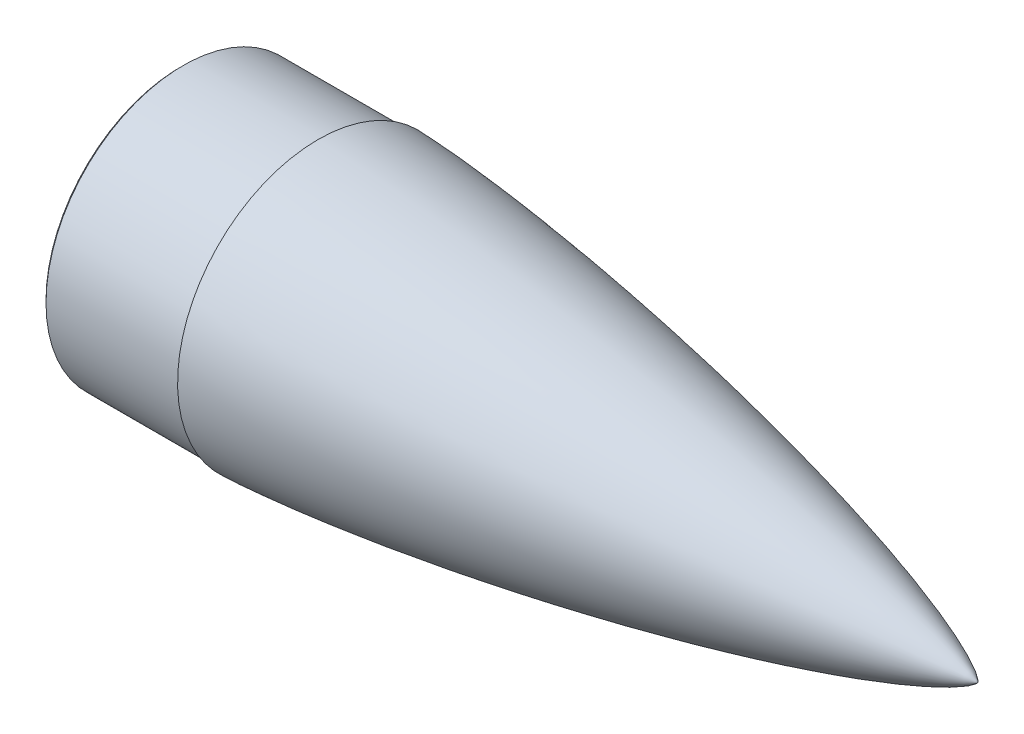
SolidWorks part; units mm, degrees
material "A-Glass Fiber"
ref_plane "Front Plane" through (0, 0, 0) normal (0, 0, 1) x (1, 0, 0)
ref_plane "Top Plane" through (0, 0, 0) normal (0, 1, 0) x (1, 0, 0)
ref_plane "Right Plane" through (0, 0, 0) normal (1, 0, 0) x (0, 0, -1)
ref_axis "Axis1" through (46.9179, 0, 0) along (-1, 0, 0)
sketch "Sketch10" plane through (0, 0, 0) normal (0, 0, 1) x (1, 0, 0)
  line L1 (-1.0327, 0) -> (486.9547, 0) construction
  line L3 (11.1125, 81.9998) -> (-84.6045, 81.9998)
  line L4 (408.9673, 0) -> (368.9673, 0)
  line L5 (-84.6045, 81.9998) -> (-84.6045, 84.9998)
  line L6 (-84.6045, 84.9998) -> (0.3953, 84.9998)
  line L7 (0.3953, 84.9998) -> (0.3953, 86.9998)
  spline S0 degree 4 poles (408.9673, 0) (408.9649, 0.0135) (408.958, 0.0399) (408.9365, 0.0905) (408.8922, 0.1741) (408.8263, 0.2756) (408.7217, 0.4158) (408.5611, 0.6051) (408.3056, 0.8724) (407.8697, 1.2753) (407.121, 1.8851) (405.8038, 2.8259) (403.4624, 4.2872) (399.3253, 6.5318) (392.4811, 9.7589) (380.6621, 14.628) (363.6372, 20.7117) (342.2152, 27.4765) (317.4285, 34.4976) (291.8793, 41.1048) (266.2105, 47.229) (240.4455, 52.9334) (214.5989, 58.2554) (188.6809, 63.2176) (165.9462, 67.2533) (146.422, 70.4938) (130.1279, 73.0449) (117.0786, 74.9942) (104.0155, 76.8485) (92.5733, 78.3845) (82.7571, 79.6356) (74.5713, 80.6322) (68.0193, 81.4008) (61.4637, 82.1394) (54.9047, 82.8464) (48.3422, 83.5199) (41.7761, 84.1578) (36.0275, 84.6822) (31.0979, 85.1052) (26.9883, 85.4387) (23.6997, 85.6932) (20.0858, 85.9584) (16.7199, 86.189) (13.6021, 86.387) (10.7327, 86.5546) (8.4366, 86.6787) (6.14, 86.7922) (4.1299, 86.8793) (2.4065, 86.9446) (1.2573, 86.979) (0.6827, 86.9949) (0.3953, 86.9998) knots 0 0 0 0 0 0.00013 0.00026 0.00052 0.0009 0.00128 0.001925 0.002882 0.004418 0.006927 0.011111 0.018279 0.030673 0.051704 0.083102 0.139909 0.202703 0.265496 0.32829 0.391083 0.453877 0.516671 0.579464 0.642258 0.673655 0.705051 0.736448 0.767845 0.799242 0.81494 0.830639 0.846337 0.862036 0.877734 0.893432 0.909131 0.924829 0.932678 0.940527 0.948377 0.956226 0.967169 0.972641 0.978113 0.983585 0.989056 0.994528 0.997264 1 1 1 1 1 construction
  spline S1 degree 4 poles (408.9673, 0) (408.9649, 0.0135) (408.958, 0.0399) (408.9365, 0.0905) (408.8922, 0.1741) (408.8263, 0.2756) (408.7217, 0.4158) (408.5611, 0.6051) (408.3056, 0.8724) (407.8697, 1.2753) (407.121, 1.8851) (405.8038, 2.8259) (403.4624, 4.2872) (399.3253, 6.5318) (392.4811, 9.7589) (380.6621, 14.628) (363.6372, 20.7117) (342.2152, 27.4765) (317.4285, 34.4976) (291.8793, 41.1048) (266.2105, 47.229) (240.4455, 52.9334) (214.5989, 58.2554) (188.6809, 63.2176) (165.9462, 67.2533) (146.422, 70.4938) (130.1279, 73.0449) (117.0786, 74.9942) (104.0155, 76.8485) (92.5733, 78.3845) (82.7571, 79.6356) (74.5713, 80.6322) (68.0193, 81.4008) (61.4637, 82.1394) (54.9047, 82.8464) (48.3422, 83.5199) (41.7761, 84.1578) (36.0275, 84.6822) (31.0979, 85.1052) (26.9883, 85.4387) (23.6997, 85.6932) (20.0858, 85.9584) (16.7199, 86.189) (13.6021, 86.387) (10.7327, 86.5546) (8.4366, 86.6787) (6.14, 86.7922) (4.1299, 86.8793) (2.4065, 86.9446) (1.2573, 86.979) (0.6827, 86.9949) (0.3953, 86.9998) knots 0 0 0 0 0 0.00013 0.00026 0.00052 0.0009 0.00128 0.001925 0.002882 0.004418 0.006927 0.011111 0.018279 0.030673 0.051704 0.083102 0.139909 0.202703 0.265496 0.32829 0.391083 0.453877 0.516671 0.579464 0.642258 0.673655 0.705051 0.736448 0.767845 0.799242 0.81494 0.830639 0.846337 0.862036 0.877734 0.893432 0.909131 0.924829 0.932678 0.940527 0.948377 0.956226 0.967169 0.972641 0.978113 0.983585 0.989056 0.994528 0.997264 1 1 1 1 1
  spline S2 degree 4 poles (368.9673, 0) (368.9653, 0.0123) (368.9594, 0.0365) (368.9406, 0.083) (368.9023, 0.1587) (368.8455, 0.2503) (368.7557, 0.3766) (368.6167, 0.5484) (368.3929, 0.7936) (368.0087, 1.1649) (367.3447, 1.7299) (366.1761, 2.6016) (364.0928, 3.96) (360.426, 6.0407) (354.4022, 9.0183) (344.043, 13.5077) (329.152, 19.1285) (310.4252, 25.3986) (288.7413, 31.9337) (266.3785, 38.1061) (243.9014, 43.8469) (221.332, 49.212) (198.684, 54.2345) (175.9669, 58.9343) (156.0346, 62.7717) (138.9133, 65.8645) (124.6221, 68.3077) (113.1754, 70.1797) (101.7151, 71.9664) (91.6754, 73.4517) (83.0615, 74.6659) (75.8775, 75.6363) (70.1269, 76.3867) (64.3728, 77.1101) (58.6152, 77.8049) (52.854, 78.4695) (47.0892, 79.1019) (42.0417, 79.6247) (37.7129, 80.0488) (34.1039, 80.385) (31.2157, 80.6428) (28.0648, 80.911) (24.6507, 81.1843) (21.4654, 81.4195) (18.5093, 81.6177) (16.0448, 81.767) (14.3191, 81.8612) (12.8395, 81.9336) (11.8527, 81.9739) (11.3593, 81.993) (11.1125, 81.9998) knots 0 0 0 0 0 0.000135 0.00027 0.00054 0.00092 0.001299 0.001947 0.002931 0.004512 0.007081 0.01138 0.018708 0.031424 0.052705 0.084103 0.14091 0.203703 0.266497 0.329291 0.392084 0.454878 0.517672 0.580465 0.643259 0.674656 0.706052 0.737449 0.768846 0.800243 0.815941 0.831639 0.847338 0.863036 0.878735 0.894433 0.910132 0.92583 0.933679 0.941528 0.949378 0.957227 0.96792 0.978613 0.98396 0.989307 0.994653 0.997327 1 1 1 1 1 construction
  spline S3 degree 4 poles (368.9673, 0) (368.9653, 0.0123) (368.9594, 0.0365) (368.9406, 0.083) (368.9023, 0.1587) (368.8455, 0.2503) (368.7557, 0.3766) (368.6167, 0.5484) (368.3929, 0.7936) (368.0087, 1.1649) (367.3447, 1.7299) (366.1761, 2.6016) (364.0928, 3.96) (360.426, 6.0407) (354.4022, 9.0183) (344.043, 13.5077) (329.152, 19.1285) (310.4252, 25.3986) (288.7413, 31.9337) (266.3785, 38.1061) (243.9014, 43.8469) (221.332, 49.212) (198.684, 54.2345) (175.9669, 58.9343) (156.0346, 62.7717) (138.9133, 65.8645) (124.6221, 68.3077) (113.1754, 70.1797) (101.7151, 71.9664) (91.6754, 73.4517) (83.0615, 74.6659) (75.8775, 75.6363) (70.1269, 76.3867) (64.3728, 77.1101) (58.6152, 77.8049) (52.854, 78.4695) (47.0892, 79.1019) (42.0417, 79.6247) (37.7129, 80.0488) (34.1039, 80.385) (31.2157, 80.6428) (28.0648, 80.911) (24.6507, 81.1843) (21.4654, 81.4195) (18.5093, 81.6177) (16.0448, 81.767) (14.3191, 81.8612) (12.8395, 81.9336) (11.8527, 81.9739) (11.3593, 81.993) (11.1125, 81.9998) knots 0 0 0 0 0 0.000135 0.00027 0.00054 0.00092 0.001299 0.001947 0.002931 0.004512 0.007081 0.01138 0.018708 0.031424 0.052705 0.084103 0.14091 0.203703 0.266497 0.329291 0.392084 0.454878 0.517672 0.580465 0.643259 0.674656 0.706052 0.737449 0.768846 0.800243 0.815941 0.831639 0.847338 0.863036 0.878735 0.894433 0.910132 0.92583 0.933679 0.941528 0.949378 0.957227 0.96792 0.978613 0.98396 0.989307 0.994653 0.997327 1 1 1 1 1
  dimension "D1" = 86.9998
  dimension "D2" = 3
  dimension "D3" = 410
  dimension "D4" = 84.9998
  dimension "D5" = 370
  dimension "D6" = 84.9998
revolve "Revolve1" add sketch "Sketch10" angle 360 about axis through (46.9179, 0, 0) along (-1, 0, 0)
chamfer "Chamfer1" distance 1.5 angle 45 1 edges at (-84.6045, 0, -84.9998)
